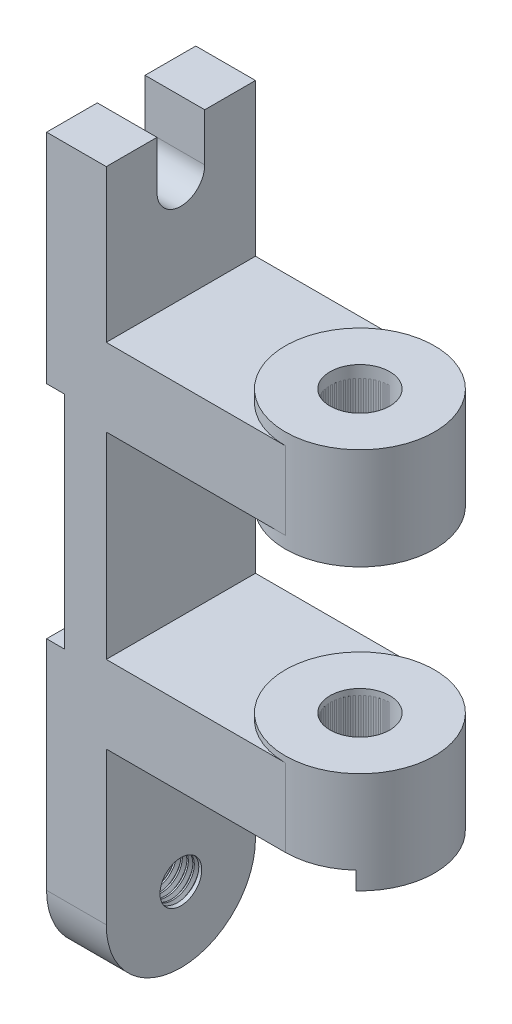
SolidWorks part; units mm, degrees
material "GG_24"
ref_plane "Front Plane" through (0, 0, 0) normal (0, 0, 1) x (1, 0, 0)
ref_plane "Top Plane" through (0, 0, 0) normal (0, 1, 0) x (1, 0, 0)
ref_plane "Right Plane" through (0, 0, 0) normal (1, 0, 0) x (0, 0, -1)
sketch "Sketch1" plane through (0, 0, 0) normal (0, 0, 1) x (1, 0, 0)
  line L0 (0, -37) -> (0, 37)
  line L1 (-6, 37) -> (-6, 110)
  line L2 (-6, 110) -> (14, 110)
  line L19 (14, 110) -> (14, 59)
  line L20 (14, -110) -> (-6, -110)
  line L21 (-6, -110) -> (-6, -37)
  line L22 (0, 37) -> (-6, 37)
  line L23 (0, -37) -> (-6, -37)
  line L24 (-72.0713, 0) -> (72.0713, 0) construction
  line L25 (14, 59) -> (74, 59)
  line L26 (74, 59) -> (74, 33)
  line L27 (74, 33) -> (14, 33)
  line L28 (74, -33) -> (14, -33)
  line L29 (74, -59) -> (74, -33)
  line L30 (14, -59) -> (74, -59)
  line L31 (14, 33) -> (14, -33)
  line L32 (14, -59) -> (14, -110)
  point P4 (0, 0)
  point P7 (0, 0)
  dimension "D1" = 220
  dimension "D2" = 20
  dimension "D3" = 14
  dimension "D4" = 26
  dimension "D5" = 66
  dimension "D6" = 60
  dimension "D7" = 74
extrude "Boss-Extrude1" add sketch "Sketch1" along normal mid plane 50
sketch "Sketch2" plane through (0, 0, 0) normal (0, 1, 0) x (1, 0, 0)
  line L0 (14, -25) -> (14, 25) construction
  circle A0 centre (74, 0) radius 25
  dimension "D1" = 50
  dimension "D2" = 60
extrude "Boss-Extrude2" add sketch "Sketch2" along normal blind 34 from offset 29 separate body
extrude "Boss-Extrude3" add sketch "Sketch2<2>" against normal blind 34 from offset 31 separate body offset against normal yes
sketch "Sketch2<2>" plane through (0, 0, 0) normal (0, 1, 0) x (1, 0, 0) same geometry as "Sketch2"
sketch "Sketch3" plane through (14, 0, 0) normal (1, 0, 0) x (0, 0, -1)
  line L0 (8, 110) -> (8, 94)
  line L1 (-25, 110) -> (25, 110) construction
  line L2 (-8, 94) -> (-8, 110)
  line L3 (0, 94) -> (0, -117.6956) construction
  line L4 (-8, 110) -> (8, 110)
  arc A0 (8, 94) -> (-8, 94) centre (0, 94) cw
  dimension "D1" = 16
  dimension "D2" = 16
extrude "Cut-Extrude1" cut sketch "Sketch3" against normal up to next (20 mm away)
sketch "Sketch4" plane through (14, 0, 0) normal (1, 0, 0) x (0, 0, -1)
  line L0 (-25, -110) -> (25, -110) construction
  circle A0 centre (0, -110) radius 25
extrude "Boss-Extrude4" add sketch "Sketch4" against normal blind 20
sketch "Sketch5" plane through (14, 0, 0) normal (1, 0, 0) x (0, 0, -1)
  circle A0 centre (0, -110) radius 7
  dimension "D1" = 14
extrude "Cut-Extrude2" cut sketch "Sketch5" against normal up to next (20 mm away)
thread "Thread1" pitch 2 method cut profile "Thread Profile1" start angle 0, offset 0, length 22, pitch 2, diameter 14
ref_plane "Plane1" through (14, -110, 7) normal (0, -1, 0) x (0, 0, 1)
sketch "Thread Profile1" plane through (14, -110, 7) normal (0, -1, 0) x (0, 0, 1)
  line L0 (0, 0) -> (0, 2) construction
  line L1 (0, 0) -> (1.0825, 0.625)
  line L2 (1.0825, 0.625) -> (1.0825, 0.875)
  line L3 (1.0825, 0.875) -> (0, 1.5)
  line L4 (1.0825, 0.75) -> (0, 0.75) construction
  line L11 (0, 0) -> (0, 1.5)
  point P2 (0, 0)
  dimension "Pitch" = 2
  dimension "Profile_Angle" = 60
  dimension "Profile_Land" = 0.25
  dimension "Profile_Height" = 1.0825
sketch "Sketch12" plane through (0, -65, 0) normal (0, -1, 0) x (1, 0, 0)
  line L0 (0, 0) -> (110.0552, 0) construction
  circle A1 centre (74, 0) radius 10
  dimension "D1" = 20
extrude "Cut-Extrude4" cut sketch "Sketch12" against normal blind 140
sketch "Sketch13" plane through (0, 0, 0) normal (0, 0, 1) x (1, 0, 0)
  line L0 (49, -65) -> (99, -65) construction
  line L1 (91, -71) -> (57, -71)
  line L2 (91, -71) -> (91, -59)
  line L4 (57, -71) -> (57, -59)
  line L5 (91, -71) -> (57, -59) construction
  line L6 (91, -59) -> (57, -71) construction
  line L8 (57, -59) -> (91, -59)
  point P0 (74, -65)
  dimension "D1" = 34
  dimension "D2" = 12
extrude "Cut-Extrude5" cut sketch "Sketch13" against normal through all both and the other way through all
